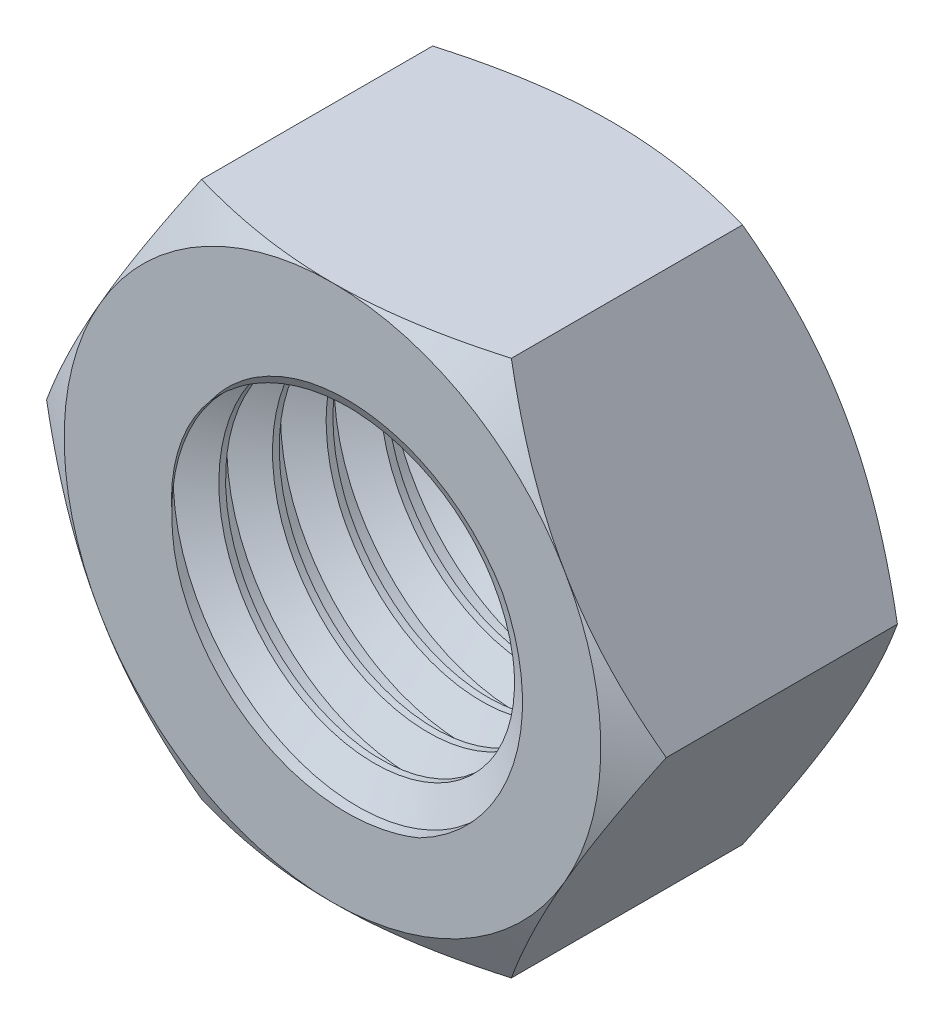
SolidWorks part; units mm, degrees
ref_plane "前视基准面" through (0, 0, 0) normal (0, 0, 1) x (1, 0, 0)
ref_plane "上视基准面" through (0, 0, 0) normal (0, 1, 0) x (1, 0, 0)
ref_plane "右视基准面" through (0, 0, 0) normal (1, 0, 0) x (0, 0, -1)
sketch "草图1" plane through (0, 0, 0) normal (0, 0, 1) x (1, 0, 0)
  line L1 (5.7735, 0) -> (2.8868, 5)
  line L2 (2.8868, 5) -> (-2.8868, 5)
  line L3 (-2.8868, 5) -> (-5.7735, 0)
  line L4 (-5.7735, 0) -> (-2.8868, -5)
  line L5 (-2.8868, -5) -> (2.8868, -5)
  line L6 (2.8868, -5) -> (5.7735, 0)
  circle A0 centre (0, 0) radius 5 construction
  dimension "D1" = 10
extrude "拉伸1" add sketch "草图1" along normal blind 5.2
sketch "草图2" plane through (0, 0, 0) normal (0, 0, -1) x (-1, 0, 0)
  circle A0 centre (0, 0) radius 5
  dimension "D1" = 10
sketch "草图3" plane through (0, 0, 0) normal (0, 1, 0) x (1, 0, 0)
  line L0 (5, 0) -> (5.7735, -0.4466)
  line L1 (5, 0) -> (-5, 0)
  line L2 (5, 0) -> (-5, 0)
  line L3 (5.7735, -5.2) -> (5.7735, 0) construction
  line L4 (5, 0) -> (5.7735, 0)
  line L5 (5.7735, 0) -> (5.7735, -0.4466)
  line L6 (0, 4.959) -> (0, -21.1771) construction
  dimension "D2" = 30
  dimension "D1" = 0
revolve "切除-旋转1" cut sketch "草图3" angle 360 about L6
sketch "草图4" plane through (0, 0, 5.2) normal (0, 0, 1) x (1, 0, 0)
  circle A0 centre (0, 0) radius 5
  dimension "D1" = 10
sketch "草图5" plane through (0, 0, 0) normal (0, 1, 0) x (1, 0, 0)
  line L0 (5, -5.2) -> (5.7735, -4.7534)
  line L1 (-5, -5.2) -> (5, -5.2)
  line L2 (-5, -5.2) -> (5, -5.2)
  line L3 (5.7735, -5.2) -> (5.7735, -0.4466) construction
  line L4 (5, -5.2) -> (5.7735, -5.2)
  line L5 (5.7735, -4.7534) -> (5.7735, -5.2)
  line L6 (0, 5.5944) -> (0, -24.6427) construction
  dimension "D2" = 30
  dimension "D1" = 0
revolve "切除-旋转2" cut sketch "草图5" angle 360 about L6
sketch "草图6" plane through (0, 0, 5.2) normal (0, 0, 1) x (1, 0, 0)
  circle A0 centre (0, 0) radius 3
  dimension "D1" = 6
extrude "切除-拉伸1" cut sketch "草图6" against normal through all
sketch "草图7" plane through (0, 0, 0) normal (1, 0, 0) x (0, 0, -1)
  line L0 (-4.9903, -3) -> (2.3037, -3) construction
  line L1 (-5.2, -3) -> (0, -3) construction
  line L2 (0, -11.5678) -> (0, -23.4371) construction
  line L3 (0, -2.5) -> (0, 2.5) construction
  line L4 (0, -5) -> (0, -2.5) construction
  line L5 (-0.125, -3.5413) -> (-0.4375, -3)
  line L6 (0.125, -3.5413) -> (0.4375, -3)
  line L7 (-0.4375, -3) -> (0.4375, -3)
  line L8 (-0.125, -3.5413) -> (0.125, -3.5413)
  dimension "D1" = 30
  dimension "D2" = 30
  dimension "D3" = 0.875
  dimension "D4" = 0.25
sketch "草图8" plane through (0, 0, 0) normal (0, 0, -1) x (-1, 0, 0)
  circle A0 centre (0, 0) radius 3
  dimension "D1" = 6
curve "螺旋线1" pitch 1 height 5.2 turns 5.2
sweep "切除-扫描1" cut profiles "草图7" path "螺旋线1"
